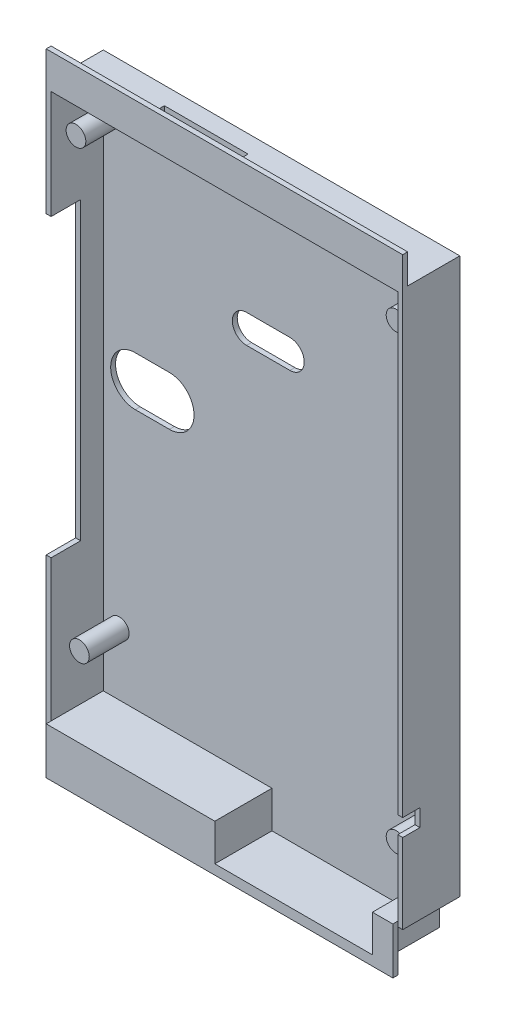
SolidWorks part; units mm, degrees
ref_plane "Plano frontal" through (0, 0, 0) normal (0, 0, 1) x (1, 0, 0)
ref_plane "Plano superior" through (0, 0, 0) normal (0, 1, 0) x (1, 0, 0)
ref_plane "Plano direito" through (0, 0, 0) normal (1, 0, 0) x (0, 0, -1)
sketch "Esboço1" plane through (0, 0, 0) normal (0, 0, 1) x (1, 0, 0)
  line L0 (11, 65.5) -> (171, 65.5) construction
  line L1 (0, 0) -> (182, 0)
  line L2 (0, 0) -> (0, 131)
  line L3 (0, 131) -> (182, 131)
  line L4 (182, 0) -> (182, 131)
  line L5 (11, 113.5) -> (171, 113.5)
  line L6 (11, 113.5) -> (11, 17.5)
  line L7 (11, 17.5) -> (171, 17.5)
  line L8 (171, 113.5) -> (171, 17.5)
  line L9 (5.7, 118.4) -> (176.3, 118.4)
  line L10 (5.7, 118.4) -> (5.7, 6.8)
  line L11 (5.7, 6.8) -> (176.3, 6.8)
  line L12 (176.3, 118.4) -> (176.3, 6.8)
  line L13 (5.9, 118.2) -> (176.1, 118.2)
  line L14 (5.9, 118.2) -> (5.9, 7)
  line L15 (5.9, 7) -> (176.1, 7)
  line L16 (176.1, 118.2) -> (176.1, 7)
  line L17 (91, 131) -> (91, 0) construction
  point P21 (91, 65.5)
  point P22 (91, 65.5)
  dimension "D1" = 131
  dimension "D2" = 182
  dimension "D3" = 160
  dimension "D4" = 96
  dimension "D5" = 170.2
  dimension "D6" = 111.2
  dimension "D7" = 0.2
  dimension "D8" = 4.7
  dimension "D9" = 0.2
  dimension "D10" = 0.2
  dimension "D11" = 0.2
  dimension "D12" = 5.1
  dimension "D13" = 5.1
  dimension "D14" = 10.5
extrude "Ressalto-extrusão1" add sketch "Esboço1" along normal blind 0.9 contours L16 L15 L14 L13
sketch "Esboço4" plane through (0, 0, 0) normal (0, 0, -1) x (-1, 0, 0)
  line L1 (-179.1, 121.2) -> (-2.9, 121.2)
  line L2 (-179.1, 121.2) -> (-179.1, 4)
  line L3 (-179.1, 4) -> (-2.9, 4)
  line L4 (-2.9, 121.2) -> (-2.9, 4)
  line L8 (-176.1, 118.2) -> (-176.1, 7) construction
  line L9 (-5.9, 118.2) -> (-176.1, 118.2) construction
  line L10 (-5.9, 7) -> (-176.1, 7) construction
  line L11 (-5.9, 118.2) -> (-5.9, 7) construction
  dimension "D1" = 3
  dimension "D2" = 3
  dimension "D3" = 3
  dimension "D4" = 3
extrude "Ressalto-extrusão3" add sketch "Esboço4" along normal blind 1
sketch "Esboço5" plane through (0, 4, 0) normal (0, -1, 0) x (1, 0, 0)
  line L0 (179.1, -1) -> (2.9, -1) construction
  line L1 (75, -1) -> (107, -1)
  line L2 (75, -1) -> (75, 0.9)
  line L3 (75, 0.9) -> (107, 0.9)
  line L4 (107, -1) -> (107, 0.9)
  line L5 (5.9, 0.9) -> (176.1, 0.9) construction
  point P8 (91, -1)
  point P9 (91, -1)
  dimension "D1" = 32
extrude "Corte-extrusão3" cut sketch "Esboço5" against normal blind 5
sketch "Esboço6" plane through (0, 0, -1) normal (0, 0, -1) x (-1, 0, 0)
  line L0 (-43.3, 106.45) -> (-42.05, 106.45) construction
  line L1 (-44, 16.15) -> (-44, 14.9) construction
  line L2 (-110.15, 109) -> (-40.75, 109) construction
  line L3 (-110.15, 109) -> (-110.15, 8.4) construction
  line L4 (-110.15, 8.4) -> (-40.75, 8.4) construction
  line L5 (-40.75, 109) -> (-40.75, 8.4) construction
  line L6 (-44, 16.15) -> (-42.75, 16.15) construction
  line L7 (-43.3, 106.45) -> (-43.3, 107.7) construction
  line L8 (-108.3, 106.45) -> (-108.3, 107.7) construction
  line L9 (-108.3, 106.45) -> (-109.55, 106.45) construction
  line L10 (-108.3, 14.75) -> (-108.3, 13.5) construction
  line L11 (-108.3, 14.75) -> (-109.55, 14.75) construction
  line L12 (-75, 9) -> (-107, 9) construction
  line L13 (-108.3, 14.75) -> (-108.3, 16) construction
  circle A0 centre (-108.3, 14.75) radius 1.25
  circle A1 centre (-108.3, 106.45) radius 1.25
  circle A2 centre (-43.3, 106.45) radius 1.25
  circle A3 centre (-44, 16.15) radius 1.25
  point P22 (-91, 9)
  dimension "D1" = 2.5
  dimension "D2" = 2.5
  dimension "D3" = 2.5
  dimension "D4" = 2.5
  dimension "D5" = 100.6
  dimension "D6" = 69.4
  dimension "D7" = 6.5
  dimension "D8" = 2
  dimension "D9" = 1.3
  dimension "D10" = 1.3
  dimension "D11" = 2.6
  dimension "D12" = 0.6
  dimension "D13" = 0.6
  dimension "D14" = 5.1
  dimension "D15" = 19.15
  dimension "D16" = 9
sketch "Esboço7" plane through (0, 0, -1) normal (0, 0, -1) x (-1, 0, 0)
  line L0 (-111.15, 121.2) -> (-40.75, 121.2)
  line L4 (-2.9, 121.2) -> (-179.1, 121.2) construction
  line L5 (-111.15, 121.2) -> (-111.15, 114.2)
  line L6 (-111.15, 114.2) -> (-40.75, 114.2)
  line L7 (-40.75, 114.2) -> (-40.75, 121.2)
  line L8 (-111.15, 114.2) -> (-111.15, 2.5)
  line L9 (-111.15, 2.5) -> (-111.15, -6)
  line L10 (-111.15, -6) -> (-40.75, -6)
  line L11 (-40.75, -6) -> (-40.75, 2.5)
  line L13 (-40.75, 114.2) -> (-40.75, 2.5)
  line L14 (-111.15, 115.2) -> (-40.75, 115.2)
  line L15 (-111.15, 2.5) -> (-108, 2.5)
  line L16 (-108, 2.5) -> (-108, -5)
  line L17 (-108, -5) -> (-74, -5)
  line L18 (-74, -5) -> (-74, 2.5)
  line L19 (-74, 2.5) -> (-40.75, 2.5)
  line L20 (-110.15, 109) -> (-110.15, 8.4) construction
  line L21 (-111.15, 3.5) -> (-107, 3.5)
  line L22 (-107, 3.5) -> (-107, -4)
  line L23 (-107, -4) -> (-75, -4)
  line L24 (-75, -4) -> (-75, 3.5)
  line L25 (-75, 3.5) -> (-40.75, 3.5)
  line L26 (-107, 9) -> (-107, 4) construction
  line L27 (-75, 9) -> (-75, 4) construction
  line L28 (-40.75, 109) -> (-40.75, 8.4) construction
  line L31 (-75, 4) -> (-2.9, 4) construction
  point P1 (0, 0)
  point P32 (-111.3116, 121.5408)
  point P33 (0, 0)
  point P34 (-40.75, 120.3542)
  point P35 (0, 0)
  point P37 (0, 0)
  line M24 (-75, 9) -> (-75, 4)
  line M25 (-75, 4) -> (-2.9, 4)
  line M27 (-2.9, 121.2) -> (-179.1, 121.2)
  line M29 (-179.1, 4) -> (-107, 4)
  line M30 (-107, 4) -> (-107, 9)
  line M31 (-107, 9) -> (-75, 9)
  dimension "D1" = 7
  dimension "D2" = 10
  dimension "D3" = 1
  dimension "D4" = 1
  dimension "D5" = 1
  dimension "D6" = 1
  dimension "D7" = 1
  dimension "D8" = 1
  dimension "D9" = 1
  dimension "D10" = 2
  dimension "D11" = 0.5
extrude "Ressalto-extrusão4" add sketch "Esboço7" along normal blind 1 contours L5 L14 L7 M27 | L14 L5 L6 L7 region at (75.95, 118.2, -1) region at (75.95, 114.7, -1)
extrude "Ressalto-extrusão5" add sketch "Esboço7<3>" along normal blind 11.6 contours L14 L5 L6 L7 region at (75.95, 114.7, -1)
sketch "Esboço7<3>" plane through (0, 0, -1) normal (0, 0, -1) x (-1, 0, 0) same geometry as "Esboço7"
extrude "Ressalto-extrusão6" add sketch "Esboço7<4>" against normal blind 1 from surface contours L13 L6 L8 M29 M30 M31 M24 M25 | L24 L25 L13 L8 L21 L22 L23 M25 M24 M31 M30 M29 | L25 L24 L23 L22 L21 L8 L15 L16 L17 L18 L19 L13 region at (75.6331, 60.2076, -1) region at (89.7827, 2.5551, -1) region at (109.075, 2.7909, -1) starting at face at (75.95, 114.7, -12.6)
sketch "Esboço7<4>" plane through (0, 0, -1) normal (0, 0, -1) x (-1, 0, 0) same geometry as "Esboço7"
extrude "Ressalto-extrusão7" add sketch "Esboço7<5>" along normal up to surface (11.6 mm away) and the other way blind 1 contours L25 L24 L23 L22 L21 L8 L15 L16 L17 L18 L19 L13 region at (109.075, 2.7909, -1) up to face at (83.475, 28.8, -12.6)
sketch "Esboço7<5>" plane through (0, 0, -1) normal (0, 0, -1) x (-1, 0, 0) same geometry as "Esboço7"
extrude "Ressalto-extrusão8" add sketch "Esboço7<6>" along normal blind 1 from surface contours L19 L18 L17 L16 L15 L9 L10 L11 region at (64.7743, -2.1213, -1) starting at face at (85.9833, 0.5, 0)
sketch "Esboço7<6>" plane through (0, 0, -1) normal (0, 0, -1) x (-1, 0, 0) same geometry as "Esboço7"
sketch "Esboço8" plane through (111.15, 0, 0) normal (1, 0, 0) x (0, 0, -1)
  line L0 (1, 121.2) -> (2, 121.2)
  line L1 (2, 121.2) -> (2, 115.2)
  line L2 (2, 115.2) -> (12.6, 115.2)
  line L3 (12.6, 115.2) -> (12.6, 2.5)
  line L4 (12.6, 2.5) -> (1, 2.5)
  line L5 (1, 2.5) -> (1, 121.2)
extrude "Ressalto-extrusão9" add sketch "Esboço8" along normal blind 1
sketch "Esboço9" plane through (40.75, 0, 0) normal (-1, 0, 0) x (0, 0, 1)
  line L0 (-2, 121.2) -> (-1, 121.2)
  line L1 (-1, 121.2) -> (-1, 2.5)
  line L2 (-1, 2.5) -> (-12.6, 2.5)
  line L3 (-12.6, 2.5) -> (-12.6, 115.2)
  line L4 (-12.6, 115.2) -> (-2, 115.2)
  line L5 (-2, 115.2) -> (-2, 121.2)
extrude "Ressalto-extrusão10" add sketch "Esboço9" along normal blind 1
sketch "Esboço11" plane through (39.75, 0, 0) normal (-1, 0, 0) x (0, 0, 1)
  line L0 (-1, 4) -> (-1, 121.2) construction
  line L1 (-1, 92.2) -> (-7, 92.2)
  line L2 (-1, 92.2) -> (-1, 32.2)
  line L3 (-1, 32.2) -> (-7, 32.2)
  line L4 (-7, 92.2) -> (-7, 32.2)
  line L5 (-2, 115.2) -> (-12.6, 115.2) construction
  dimension "D1" = 23
  dimension "D2" = 60
  dimension "D3" = 6
extrude "Corte-extrusão4" cut sketch "Esboço11" against normal blind 1
sketch "Esboço12" plane through (112.15, 0, 0) normal (1, 0, 0) x (0, 0, -1)
  line L0 (1, 22.2068) -> (4.5, 22.2068)
  line L1 (1, 121.2) -> (1, 4) construction
  line L2 (4.5, 22.2068) -> (4.5, 18.7068)
  line L3 (4.5, 18.7068) -> (1, 18.7068)
  line L4 (1, 18.7068) -> (1, 22.2068)
  dimension "D1" = 3.5
  dimension "D2" = 3.5
extrude "Corte-extrusão5" cut sketch "Esboço12" against normal blind 1
sketch "Esboço13" plane through (0, 115.2, 0) normal (0, 1, 0) x (1, 0, 0)
  line L0 (39.75, 2) -> (112.15, 2) construction
  line L1 (72.75, 2) -> (55.75, 2)
  line L2 (72.75, 2) -> (72.75, 9)
  line L3 (72.75, 9) -> (55.75, 9)
  line L4 (55.75, 2) -> (55.75, 9)
  line L5 (39.75, 2) -> (39.75, 12.6) construction
  point P8 (72.75, 5.5)
  dimension "D1" = 16
  dimension "D2" = 17
  dimension "D3" = 7
extrude "Corte-extrusão6" cut sketch "Esboço13" against normal blind 1
sketch "Esboço14" plane through (0, 0, -12.6) normal (0, 0, -1) x (-1, 0, 0)
  line L0 (-54.1785, 61.2) -> (-47.2458, 61.2) construction
  line L1 (-54.1785, 66.2) -> (-47.2458, 66.2)
  line L2 (-54.1785, 56.2) -> (-47.2458, 56.2)
  line L4 (-39.75, 121.2) -> (-112.15, 121.2) construction
  arc A0 (-54.1785, 66.2) -> (-54.1785, 56.2) centre (-54.1785, 61.2) ccw
  arc A1 (-47.2458, 56.2) -> (-47.2458, 66.2) centre (-47.2458, 61.2) ccw
  point P2 (-50.7121, 61.2)
  dimension "D1" = 65
  dimension "D3" = 55
extrude "Corte-extrusão7" cut sketch "Esboço14" against normal blind 1
sketch "Esboço15" plane through (0, 0, -12.6) normal (0, 0, -1) x (-1, 0, 0)
  line L0 (-77.25, 81.7) -> (-71.25, 81.7) construction
  line L1 (-77.25, 83.2) -> (-71.25, 83.2) construction
  line L2 (-77.25, 80.2) -> (-71.25, 80.2) construction
  line L3 (-39.75, 121.2) -> (-112.15, 121.2) construction
  line L4 (-78.65, 81.7) -> (-69.85, 81.7) construction
  line L5 (-78.65, 84.6) -> (-69.85, 84.6)
  line L6 (-78.65, 78.8) -> (-69.85, 78.8)
  arc A0 (-77.25, 83.2) -> (-77.25, 80.2) centre (-77.25, 81.7) ccw construction
  arc A1 (-71.25, 80.2) -> (-71.25, 83.2) centre (-71.25, 81.7) ccw construction
  arc A2 (-78.65, 84.6) -> (-78.65, 78.8) centre (-78.65, 81.7) ccw
  arc A3 (-69.85, 78.8) -> (-69.85, 84.6) centre (-69.85, 81.7) ccw
  point P2 (-74.25, 81.7)
  point P11 (-74.25, 81.7)
  point P16 (0, 0)
  point P17 (-69.75, 81.7)
  point P18 (-78.75, 81.7)
  point P19 (-75.75, 81.7)
  dimension "D3" = 6
  dimension "D1" = 3
  dimension "D2" = 39.5
  dimension "D4" = 39
extrude "Corte-extrusão8" cut sketch "Esboço15" against normal blind 1
sketch "Esboço17" plane through (179.1, 0, 0) normal (1, 0, 0) x (0, 0, -1)
  line L1 (1, 4) -> (-39.8076, 4)
  line L2 (1, 4) -> (1, 157.8288)
  line L3 (1, 157.8288) -> (-39.8076, 157.8288)
  line L4 (-39.8076, 4) -> (-39.8076, 157.8288)
extrude "Corte-extrusão9" cut sketch "Esboço17" against normal through all both and the other way through all
sketch "Esboço18" plane through (0, 0, -11.6) normal (0, 0, 1) x (1, 0, 0)
  circle A0 centre (43.3, 106.45) radius 2
  circle A1 centre (108.3, 106.45) radius 2
  circle A2 centre (108.3, 14.75) radius 2
  circle A3 centre (44, 16.15) radius 2
  dimension "D1" = 4
  dimension "D2" = 4
  dimension "D3" = 4
  dimension "D4" = 4
extrude "Ressalto-extrusão11" add sketch "Esboço18" along normal blind 8.1
